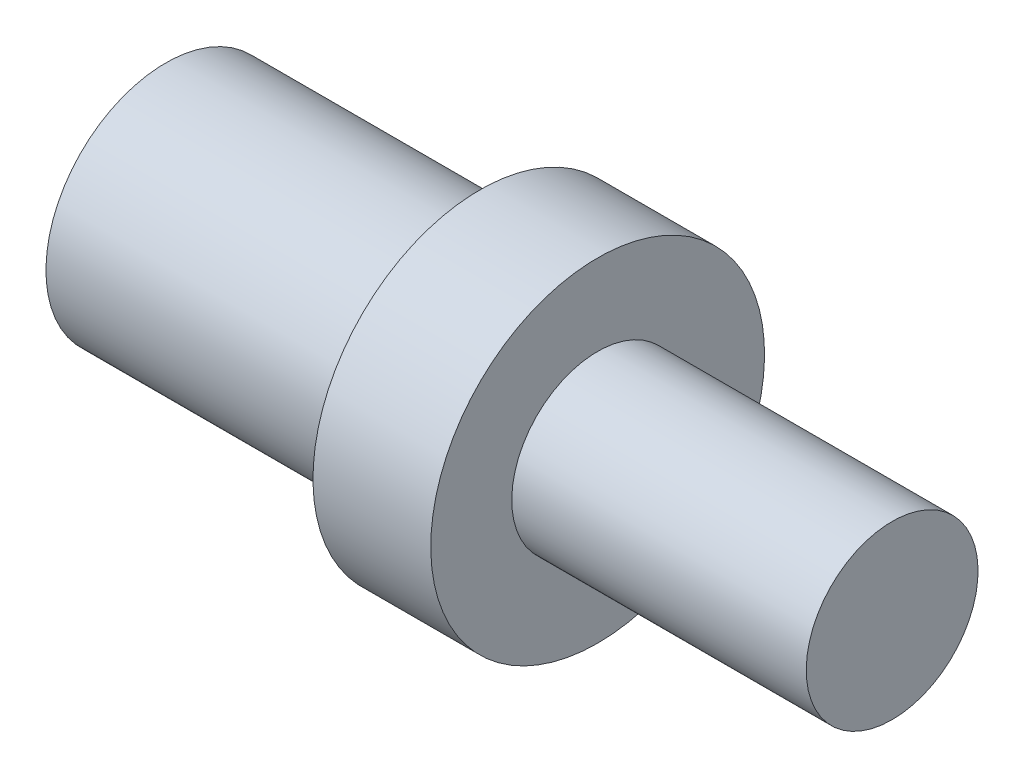
SolidWorks part; units mm, degrees
ref_plane "XY" through (0, 0, 0) normal (0, 0, 1) x (1, 0, 0)
ref_plane "XZ" through (0, 0, 0) normal (0, 1, 0) x (1, 0, 0)
ref_plane "YZ" through (0, 0, 0) normal (1, 0, 0) x (0, 0, -1)
ref_axis "X" through (-88.99, 0, 0) along (1, 0, 0)
ref_axis "Y" through (0, -55, 0) along (0, 1, 0)
ref_axis "Z" through (0, 0, 55) along (0, 0, -1)
sketch "Sketch1" plane through (0, 0, 0) normal (0, 0, 1) x (1, 0, 0)
  line L0 (0, 0) -> (0, 5.5562) construction
  line L1 (0, 10.795) -> (-7.62, 10.795)
  line L2 (-7.62, 10.795) -> (-7.62, 7.747)
  line L3 (-7.62, 7.747) -> (-27.94, 7.747)
  line L4 (-27.94, 7.747) -> (-27.94, 0)
  line L5 (-27.94, 0) -> (19.05, 0)
  line L6 (19.05, 0) -> (19.05, 5.5562)
  line L7 (19.05, 5.5562) -> (0, 5.5562)
  line L8 (0, 5.5562) -> (0, 10.795)
  dimension "D1" = 27.94
  dimension "D2" = 5.5562
  dimension "D3" = 7.747
  dimension "D4" = 10.795
  dimension "D5" = 7.62
  dimension "D6" = 19.05
revolve "Revolve1" add sketch "Sketch1" angle 360 about L5
